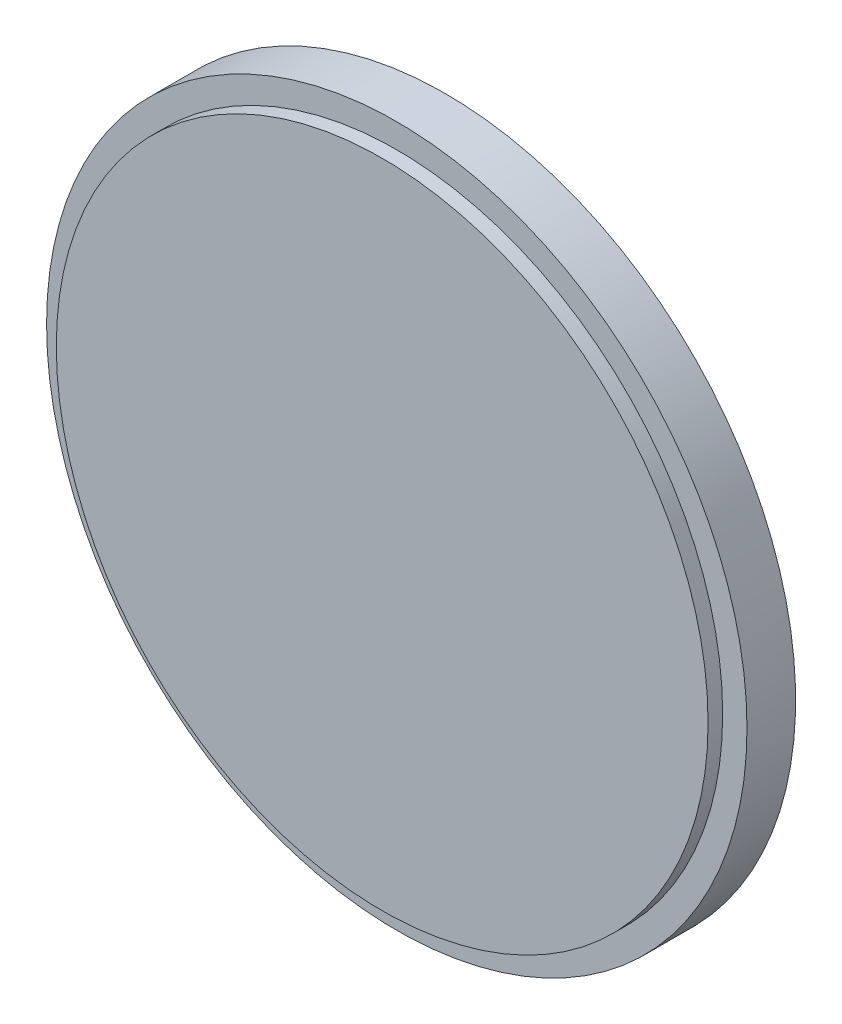
SolidWorks part; units mm, degrees
material "Liga 1060"
ref_plane "Plano frontal" through (0, 0, 0) normal (0, 0, 1) x (1, 0, 0)
ref_plane "Plano superior" through (0, 0, 0) normal (0, 1, 0) x (1, 0, 0)
ref_plane "Plano direito" through (0, 0, 0) normal (1, 0, 0) x (0, 0, -1)
sketch "Esboço1" plane through (0, 0, 0) normal (0, 0, 1) x (1, 0, 0)
  circle A0 centre (0, 0) radius 32.5
  circle A1 centre (0, 0) radius 35
extrude "Ressalto-extrusão1" add sketch "Esboço1" along normal blind 8
sketch "Esboço2" plane through (0, 0, 8) normal (0, 0, 1) x (1, 0, 0)
  circle A0 centre (0, 0) radius 32.5
extrude "Ressalto-extrusão2" add sketch "Esboço2" against normal blind 3
sketch "Esboço3" plane through (0, 0, 8) normal (0, 0, 1) x (1, 0, 0)
  circle A0 centre (0, 0) radius 2.5
extrude "Corte-extrusão1" cut sketch "Esboço3" against normal blind 3
sketch "Esboço4" plane through (0, 0, 5) normal (0, 0, -1) x (-1, 0, 0)
  circle A0 centre (0, 0) radius 37
  circle A1 centre (0, 0) radius 35
extrude "Ressalto-extrusão3" add sketch "Esboço4" against normal through all and the other way through all
sketch "Esboço5" plane through (0, 0, 0) normal (0, 1, 0) x (1, 0, 0)
  line L0 (-37, -1) -> (-37, -7)
  line L1 (-37, -4) -> (-13.2615, -4)
  line L2 (-35.2, -4) -> (-35.2, -1)
  line L3 (-35.2, -1) -> (-37, -1)
  line L4 (-35.2, -4) -> (-35.2, -7)
  line L5 (-35.2, -7) -> (-37, -7)
revolve "Corte-Revolução1" cut sketch "Esboço5" angle 360 about axis through (0, 0, 8) along (0, 0, -1) region at (-36.1, 0, 2.5) region at (-36.1, 0, 5.5)
sketch "Esboço6" plane through (0, 0, 5) normal (0, 0, -1) x (-1, 0, 0)
  circle A0 centre (0, 0) radius 12.55
  dimension "D1" = 25.1
extrude "Ressalto-extrusão4" add sketch "Esboço6" along normal blind 5
sketch "Esboço7" plane through (0, 0, 0) normal (0, 0, -1) x (-1, 0, 0)
  circle A0 centre (0, 0) radius 7.55
  dimension "D1" = 15.1
extrude "Corte-extrusão2" cut sketch "Esboço7" against normal through all both and the other way through all
sketch "Esboço8" plane through (0, 0, 8) normal (0, 0, 1) x (1, 0, 0)
  circle A0 centre (0, 0) radius 37
  circle A1 centre (0, 0) radius 32.5
  dimension "D1" = 74
extrude "Ressalto-extrusão5" add sketch "Esboço8" against normal up to surface (8 mm away) up to face at (32.5, 0, 0)
sketch "Esboço9" plane through (0, 0, 8) normal (0, 0, 1) x (1, 0, 0)
  circle A0 centre (0, 0) radius 37
  circle A1 centre (0, 0) radius 33.5
extrude "Corte-extrusão8" cut sketch "Esboço9" against normal blind 1.5
sketch "Esboço12" plane through (0, 0, 0) normal (0, 0, -1) x (-1, 0, 0)
  circle A0 centre (0, 0) radius 37
  circle A1 centre (0, 0) radius 33.5
  dimension "D1" = 74
extrude "Corte-extrusão9" cut sketch "Esboço12" against normal blind 1.5
sketch "Esboço13" plane through (0, 0, 1.5) normal (0, 0, -1) x (-1, 0, 0)
  circle A1 centre (0, 0) radius 36
  circle A2 centre (0, 0) radius 37
extrude "Corte-extrusão10" cut sketch "Esboço13" against normal blind 10
sketch "Esboço14" plane through (0, 0, 6.5) normal (0, 0, 1) x (1, 0, 0)
  circle A0 centre (0, 0) radius 37
  circle A1 centre (0, 0) radius 36
  circle A3 centre (0, 0) radius 36
  circle A6 centre (0, 0) radius 36
  circle M3 centre (0, 0) radius 36
  dimension "D1" = 0
extrude "Ressalto-extrusão6" add sketch "Esboço14" against normal up to surface (5 mm away) contours A0 M3 region at (-36.8953, 0, 6.5) up to face at (-33.5, 0, 1.5)
sketch "Esboço15" plane through (0, 0, 0) normal (0, 0, -1) x (-1, 0, 0)
  circle A0 centre (0, 0) radius 12.55
extrude "Corte-extrusão11" cut sketch "Esboço15" against normal through all
sketch "Esboço16" plane through (0, 0, 5) normal (0, 0, -1) x (-1, 0, 0)
  circle A0 centre (0, 0) radius 12.55 construction
  circle A1 centre (0, 0) radius 12.55
extrude "Ressalto-extrusão7" add sketch "Esboço16" against normal through all
sketch "Esboço17" plane through (0, 0, 5) normal (0, 0, -1) x (-1, 0, 0)
  circle A0 centre (0, 0) radius 10
  dimension "D1" = 20
extrude "Ressalto-extrusão8" add sketch "Esboço17" along normal blind 16
sketch "Esboço18" plane through (0, 0, -11) normal (0, 0, -1) x (-1, 0, 0)
  circle A0 centre (0, 0) radius 3.3
  dimension "D1" = 6.6
extrude "Corte-extrusão12" cut sketch "Esboço18" against normal blind 16
sketch "Esboço19" plane through (0, 0, -11) normal (0, 0, -1) x (-1, 0, 0)
  line L0 (0, -3.3) -> (0, -5.3) construction
  line L1 (-2.975, -5.3) -> (2.975, -5.3)
  line L2 (2.975, -5.3) -> (2.975, -7.95)
  line L3 (2.975, -7.95) -> (-2.975, -7.95)
  line L4 (-2.975, -7.95) -> (-2.975, -5.3)
  line L5 (-3.3, 0) -> (3.3, 0) construction
  line L6 (-2.975, 7.95) -> (-2.975, 5.3)
  line L7 (2.975, 7.95) -> (-2.975, 7.95)
  line L8 (2.975, 5.3) -> (2.975, 7.95)
  line L9 (-2.975, 5.3) -> (2.975, 5.3)
  circle A1 centre (0, 0) radius 3.3 construction
  circle A2 centre (0, 0) radius 3.3 construction
  point P12 (0, -5.3)
  point P19 (0, 5.3)
  dimension "D1" = 2
  dimension "D2" = 5.95
  dimension "D3" = 2.65
extrude "Corte-extrusão13" cut sketch "Esboço19" against normal blind 8
sketch "Esboço23" plane through (0, 0, 1.5) normal (0, 0, -1) x (-1, 0, 0)
  circle A0 centre (0, 0) radius 36
  circle A1 centre (0, 0) radius 37 construction
  circle A2 centre (0, 0) radius 37
  dimension "D1" = 72
extrude "Corte-extrusão15" cut sketch "Esboço23" against normal through all
sketch "Esboço24" plane through (0, 0, -11) normal (0, 0, -1) x (-1, 0, 0)
  line L0 (0, 0) -> (0, 1.1) construction
  line L1 (-1.2298, 1.1) -> (1.2298, 1.1)
  arc A0 (-1.2298, 1.1) -> (1.2298, 1.1) centre (0, 0) ccw
  circle A1 centre (0, 0) radius 3.3 construction
  circle A2 centre (0, 0) radius 3.3
  point P7 (0, 1.1)
  dimension "D1" = 3.3
  dimension "D2" = 1.1
extrude "Ressalto-extrusão9" add sketch "Esboço24" against normal blind 11
sketch "Esboço21" plane through (0, 5.3, 0) normal (0, 1, 0) x (1, 0, 0)
  line L0 (0, 11) -> (0, 8.5) construction
  line L1 (-2.975, 11) -> (2.975, 11) construction
  circle A0 centre (0, 6.85) radius 1.65
  dimension "D2" = 3.3
  dimension "D1" = 2.5
extrude "Corte-extrusão14" cut sketch "Esboço21" against normal through all both and the other way through all
